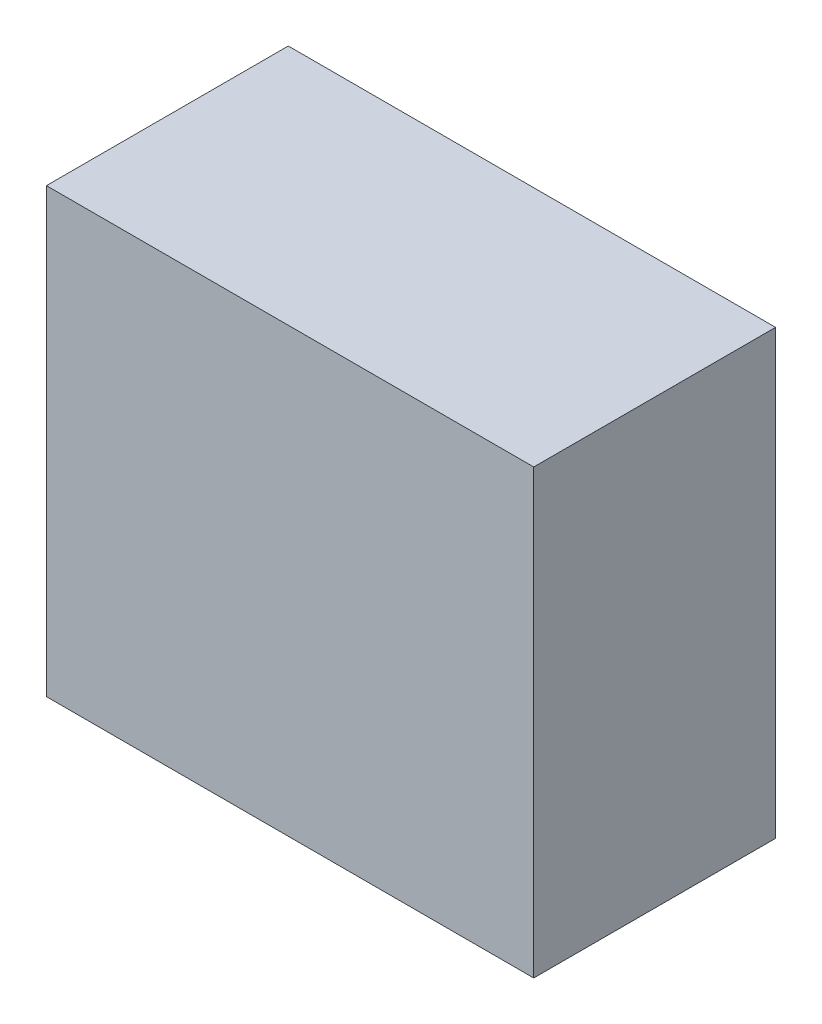
SolidWorks part; units mm, degrees
ref_plane "Front Plane" through (0, 0, 0) normal (0, 0, 1) x (1, 0, 0)
ref_plane "Top Plane" through (0, 0, 0) normal (0, 1, 0) x (1, 0, 0)
ref_plane "Right Plane" through (0, 0, 0) normal (1, 0, 0) x (0, 0, -1)
sketch "Sketch1" plane through (0, 0, 0) normal (0, 1, 0) x (1, 0, 0)
  line L1 (-20.15, -10) -> (20.15, -10)
  line L2 (-20.15, -10) -> (-20.15, 10)
  line L3 (-20.15, 10) -> (20.15, 10)
  line L4 (20.15, -10) -> (20.15, 10)
  line L5 (-20.15, -10) -> (20.15, 10) construction
  line L6 (-20.15, 10) -> (20.15, -10) construction
  point P0 (0, 0)
  dimension "D1" = 40.3
  dimension "D2" = 20
extrude "Boss-Extrude1" add sketch "Sketch1" along normal blind 36.6
